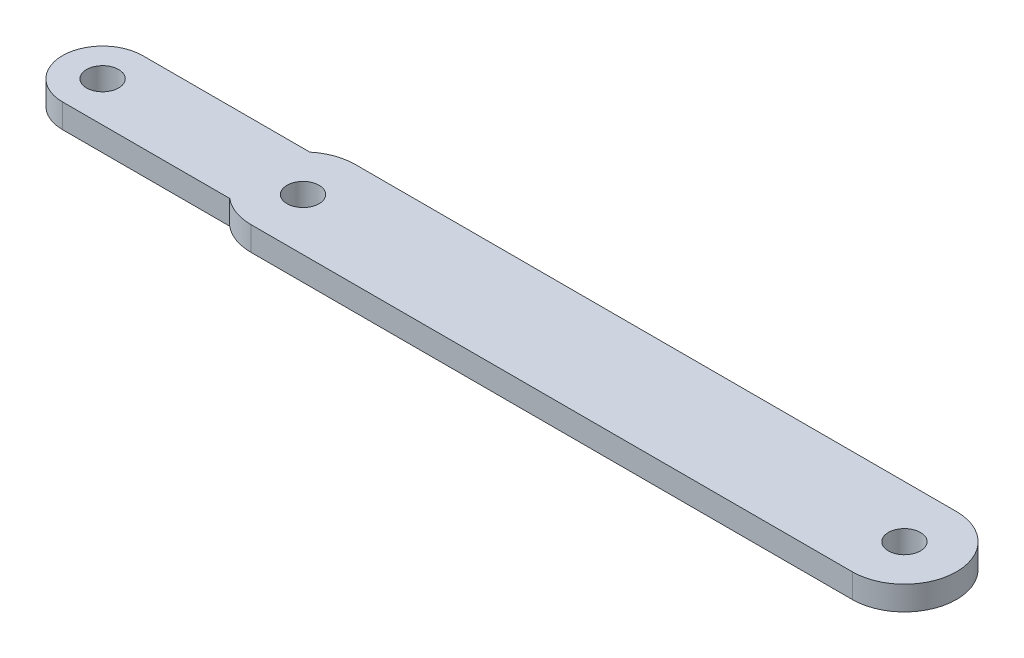
SolidWorks part; units mm, degrees
ref_plane "Front Plane" through (0, 0, 0) normal (0, 0, 1) x (1, 0, 0)
ref_plane "Top Plane" through (0, 0, 0) normal (0, 1, 0) x (1, 0, 0)
ref_plane "Right Plane" through (0, 0, 0) normal (1, 0, 0) x (0, 0, -1)
sketch "Sketch2" plane through (0, 0, 0) normal (0, 1, 0) x (1, 0, 0)
  line L1 (12.5936, 198.8185) -> (87.5936, 198.8185)
  line L3 (12.5936, 185.8185) -> (87.5936, 185.8185)
  line L4 (12.5936, 187.3185) -> (-12.4064, 187.3185)
  line L6 (12.5936, 197.3185) -> (-12.4064, 197.3185)
  arc A0 (87.5936, 198.8185) -> (87.5936, 185.8185) centre (87.5936, 192.3185) cw
  circle A1 centre (87.5936, 192.3185) radius 2
  arc A2 (12.5936, 198.8185) -> (12.5936, 185.8185) centre (12.5936, 192.3185) ccw
  arc A3 (-12.4064, 197.3185) -> (-12.4064, 187.3185) centre (-12.4064, 192.3185) ccw
  circle A4 centre (-12.4064, 192.3185) radius 2
  circle A5 centre (12.5936, 192.3185) radius 2
  dimension "D3" = 4
  dimension "D7" = 4
  dimension "D8" = 4
  dimension "D1" = 75
  dimension "D2" = 13
  dimension "D4" = 1.5
  dimension "D5" = 1.5
  dimension "D6" = 25
extrude "Boss-Extrude1" add sketch "Sketch2" along normal blind 3 contours L6 A3 L4 A2 A4 | L1 A2 L3 A0 A5 A1 region at (50.0936, 0, -192.3185) region at (-4.3414, 0, -192.3185)
